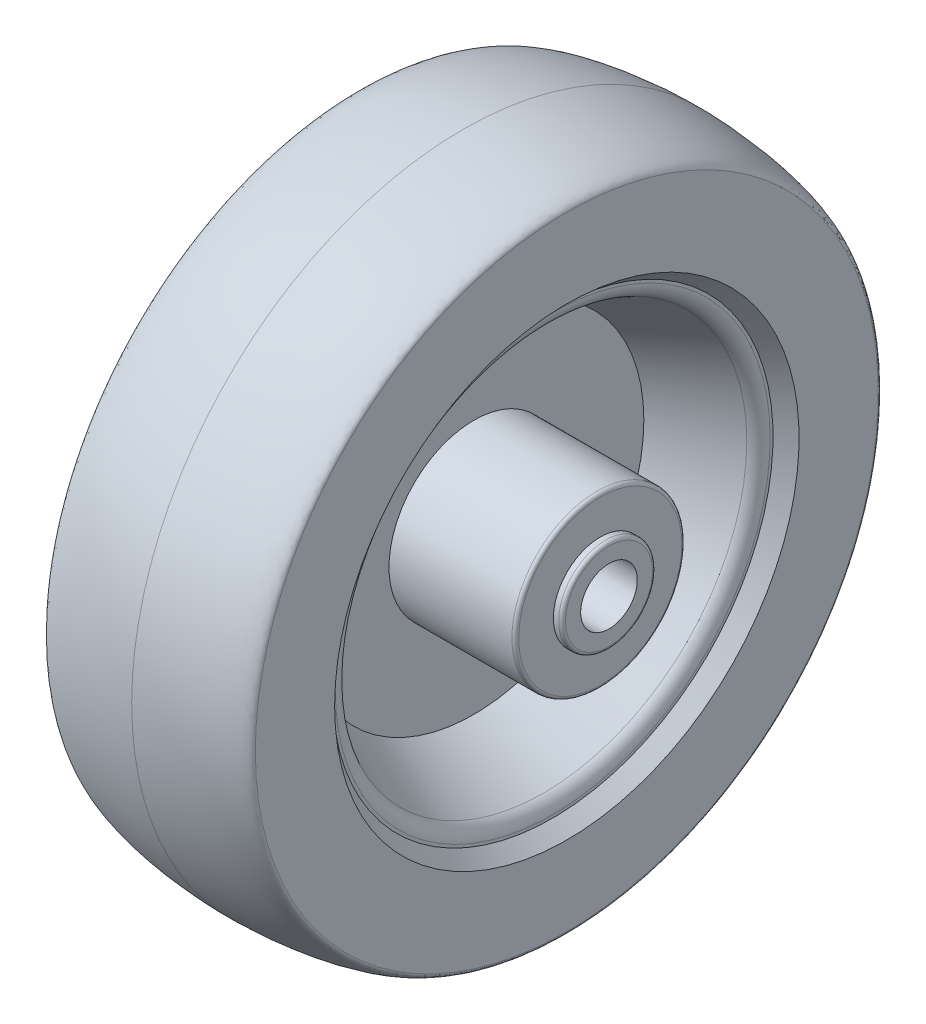
SolidWorks part; units mm, degrees
ref_plane "Front Plane" through (0, 0, 0) normal (0, 0, 1) x (1, 0, 0)
ref_plane "Top Plane" through (0, 0, 0) normal (0, 1, 0) x (1, 0, 0)
ref_plane "Right Plane" through (0, 0, 0) normal (1, 0, 0) x (0, 0, -1)
sketch "Sketch5" plane through (0, 0, 0) normal (0, 0, 1) x (1, 0, 0)
  line L0 (-23.2791, 0) -> (-23.2791, 69.85)
  line L1 (0, -1000) -> (0, 49000) construction
  line L2 (-23.2791, 0) -> (23.2791, 0) construction
  line L3 (23.2791, 0) -> (23.2791, 69.85)
  line L4 (-23.2791, 73.6345) -> (-23.2791, 66.0655) construction
  line L5 (2.3783, 74.295) -> (-2.3783, 74.295) construction
  line L6 (-23.2791, 0) -> (23.2791, 0)
  spline S0 degree 3 poles (-23.2791, 69.85) (-23.2791, 72.068) (-10.5362, 74.295) (0, 74.295) knots 0 0 0 0 1 1 1 1
  spline S1 degree 3 poles (23.2791, 69.85) (23.2791, 72.068) (10.5362, 74.295) (0, 74.295) knots 0 0 0 0 1 1 1 1
  point P8 (0, 0)
  dimension "D1" = 74.295
  dimension "D2" = 69.85
  dimension "D3" = 46.5582
revolve "Revolve1" add sketch "Sketch5" angle 360 about L6
sketch "Sketch7" plane through (0, 0, 0) normal (0, 1, 0) x (1, 0, 0)
  line L0 (-1000, 0) -> (49000, 0) construction
  line L1 (2.4511, 0) -> (2.4511, 38.1)
  line L2 (2.4511, 38.1) -> (18.0789, 45.5535)
  line L3 (20.1041, 48.7632) -> (20.1041, 49.4128)
  line L4 (20.1041, 49.4128) -> (23.2791, 52.07)
  line L5 (23.2791, -69.85) -> (23.2791, 69.85) construction
  line L6 (23.2791, 52.07) -> (23.2791, 0)
  line L7 (2.4511, 0) -> (23.2791, 0)
  arc A0 (18.0789, 45.5535) -> (20.1041, 48.7632) centre (16.5481, 48.7632) ccw
  point P12 (20.1041, 46.5194)
  dimension "D3" = 19.558
  dimension "D7" = 3.556
  dimension "D1" = 52.07
  dimension "D2" = 4.1402
  dimension "D4" = 38.1
  dimension "D5" = 20.828
  dimension "D6" = 3.175
revolve "Cut-Revolve2" cut sketch "Sketch7" angle 360 about L0
mirror "Mirror1" about plane through (0, 0, 0) normal (1, 0, 0) of "Cut-Revolve2"
sketch "Sketch8" plane through (2.4511, 0, 0) normal (1, 0, 0) x (0, 0, -1)
  circle A1 centre (0, 0) radius 19.05
  dimension "D1" = 38.1
extrude "Boss-Extrude1" add sketch "Sketch8" along normal blind 28.321
sketch "Sketch9" plane through (30.7721, 0, 0) normal (1, 0, 0) x (0, 0, -1)
  circle A0 centre (0, 0) radius 10.5156
  dimension "D1" = 21.0312
extrude "Boss-Extrude2" add sketch "Sketch9" along normal blind 1.9558
fillet "Fillet4" radius 0.762 2 edges at (32.7279, 0, -10.5156) (30.7721, 0, -19.05)
mirror "Mirror2" about plane through (0, 0, 0) normal (1, 0, 0) of "Fillet4", "Boss-Extrude2", "Boss-Extrude1"
sketch "Sketch10" plane through (-32.7279, 0, 0) normal (-1, 0, 0) x (0, 0, 1)
  circle A0 centre (0, 0) radius 6.35
  dimension "D1" = 12.7
extrude "Cut-Extrude5" cut sketch "Sketch10" against normal through all
